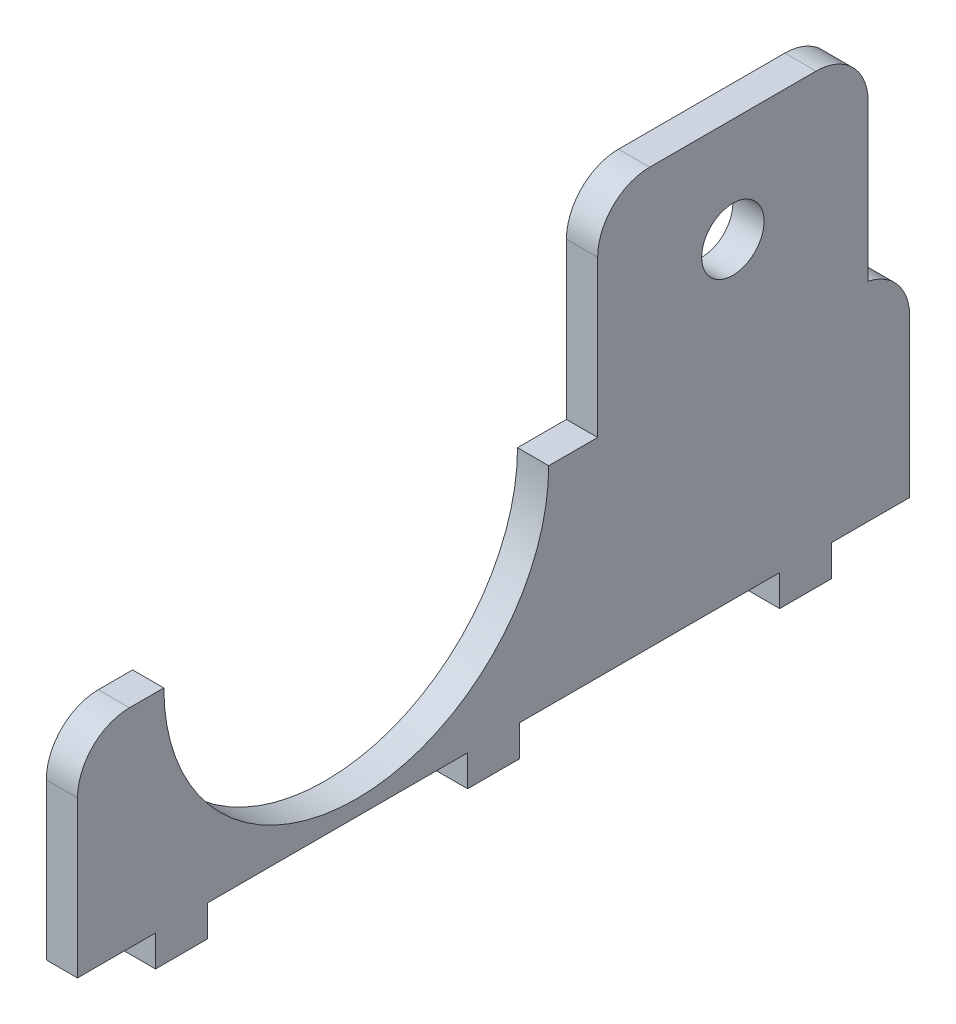
SolidWorks part; units mm, degrees
ref_plane "Front Plane" through (0, 0, 0) normal (0, 0, 1) x (1, 0, 0)
ref_plane "Top Plane" through (0, 0, 0) normal (0, 1, 0) x (1, 0, 0)
ref_plane "Right Plane" through (0, 0, 0) normal (1, 0, 0) x (0, 0, -1)
ref_plane "Plane2" through (0, -2, 0) normal (0, 1, 0) x (1, 0, 0)
sketch "Sketch1" plane through (0, 0, 0) normal (1, 0, 0) x (0, 0, -1)
  line L0 (32.5, 15) -> (-47.5, 15)
  line L1 (32.5, -25) -> (-47.5, -25)
  line L2 (32.5, -25) -> (32.5, 15)
  line L4 (-47.5, -25) -> (-47.5, 15)
  point P0 (0, 0)
  dimension "D1" = 40
  dimension "D2" = 80
extrude "Boss-Extrude1" add sketch "Sketch1" along normal blind 3
sketch "Sketch8" plane through (0, 0, 0) normal (-1, 0, 0) x (0, 0, 1)
  line L0 (-32.5, -25) -> (-32.5, 15) construction
  line L1 (39.2, -5) -> (47.5, -5)
  line L3 (47.5, -25) -> (-32.5, -25) construction
  line L4 (47.5, 15) -> (47.5, -25) construction
  line L5 (-32.5, 15) -> (47.5, 15) construction
  line L8 (2.2, 15) -> (39.2, 15)
  line L10 (39.2, 15) -> (47.5, 15)
  line L11 (47.5, -5) -> (47.5, 15)
  line L12 (2.2, -5) -> (-2.5, -5)
  line L14 (2.2, 15) -> (-2.5, 15)
  line L15 (-2.5, -5) -> (-2.5, 15)
  line L16 (-32.5, -5) -> (-28.5, -5)
  line L17 (-32.5, -5) -> (-32.5, 15)
  line L18 (-32.5, 15) -> (-28.5, 15)
  line L19 (-28.5, -5) -> (-28.5, 15)
  arc A0 (2.2, -5) -> (39.2, -5) centre (20.7, -5) ccw
  circle A2 centre (-15.5, 5) radius 3
  dimension "D1" = 37
  dimension "D4" = 36.2
  dimension "D6" = 6
  dimension "D2" = 20
  dimension "D3" = 26.8
  dimension "D5" = 10
  dimension "D7" = 13
  dimension "D8" = 13
extrude "Cut-Extrude4" cut sketch "Sketch8" against normal through all
fillet "Fillet1" radius 5 4 edges at (1.5, -5, 47.5) (1.5, 15, -2.5) (1.5, -5, -32.5) (1.5, 15, -28.5)
sketch "Sketch3" plane through (0, -25, 0) normal (0, -1, 0) x (1, 0, 0)
  line L0 (0, 47.5) -> (0, -32.5) construction
  line L5 (3, 47.5) -> (3, -32.5) construction
  line L7 (3, 47.5) -> (0, 47.5) construction
  line L20 (0, 40) -> (3, 40)
  line L21 (0, 40) -> (0, 35)
  line L22 (0, 35) -> (3, 35)
  line L23 (3, 40) -> (3, 35)
  dimension "D1" = 7.5
  dimension "D5" = 5
extrude "Boss-Extrude2" add sketch "Sketch3" along normal blind 3
pattern_linear "LPattern1" count 3 spacing 30 along (0, 0, -1) of "Boss-Extrude2"
